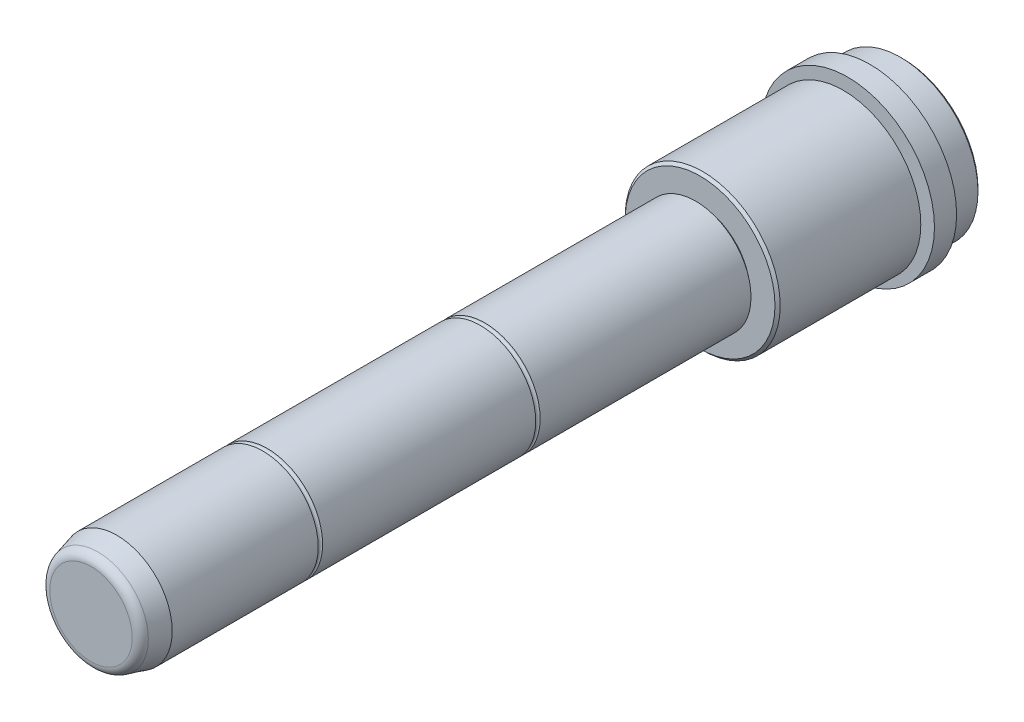
SolidWorks part; units mm, degrees
ref_plane "Płaszczyzna przednia" through (0, 0, 0) normal (0, 0, 1) x (1, 0, 0)
ref_plane "Płaszczyzna górna" through (0, 0, 0) normal (0, 1, 0) x (1, 0, 0)
ref_plane "Płaszczyzna prawa" through (0, 0, 0) normal (1, 0, 0) x (0, 0, -1)
sketch "Szkic1" plane through (0, 0, 0) normal (1, 0, 0) x (0, 0, -1)
  line L0 (-9, 0) -> (-9, 21)
  line L1 (-9, 21) -> (0, 21)
  line L2 (0, 21) -> (0, 0)
  line L3 (0, 0) -> (-9, 0)
  line L4 (0, 0) -> (-9, 0) construction
sketch "Szkic2" plane through (0, 0, 0) normal (1, 0, 0) x (0, 0, -1)
  line L0 (-0.7071, 21) -> (0, 20.2929)
  line L1 (0, 20.2929) -> (0, 21)
  line L2 (0, 21) -> (-0.7071, 21)
  line L3 (0, 0) -> (-9, 0) construction
sketch "Szkic3" plane through (0, 0, 0) normal (1, 0, 0) x (0, 0, -1)
  line L0 (-9, 18.9) -> (-7.8, 18.9)
  line L1 (-7.8, 18.9) -> (-7.8, 21)
  line L2 (-7.8, 21) -> (-9, 21)
  line L3 (-9, 21) -> (-9, 18.9)
  line L4 (0, 0) -> (-9, 0) construction
sketch "Szkic4" plane through (0, 0, 0) normal (1, 0, 0) x (0, 0, -1)
  line L0 (-15, 0) -> (-15, 23.5)
  line L1 (-15, 23.5) -> (-9, 23.5)
  line L2 (-9, 23.5) -> (-9, 0)
  line L3 (-9, 0) -> (-15, 0)
  line L4 (-9, 0) -> (-15, 0) construction
sketch "Szkic5" plane through (0, 0, 0) normal (1, 0, 0) x (0, 0, -1)
  line L0 (-55, 0) -> (-55, 21)
  line L1 (-55, 21) -> (-15, 21)
  line L2 (-15, 21) -> (-15, 0)
  line L3 (-15, 0) -> (-55, 0)
  line L4 (-15, 0) -> (-55, 0) construction
sketch "Szkic6" plane through (0, 0, 0) normal (1, 0, 0) x (0, 0, -1)
  line L0 (-16.2, 18.9) -> (-15, 18.9)
  line L1 (-15, 18.9) -> (-15, 21)
  line L2 (-15, 21) -> (-16.2, 21)
  line L3 (-16.2, 21) -> (-16.2, 18.9)
  line L4 (-15, 0) -> (-61, 0) construction
sketch "Szkic7" plane through (0, 0, 0) normal (1, 0, 0) x (0, 0, -1)
  line L0 (-55, 20.2929) -> (-54.2929, 21)
  line L1 (-54.2929, 21) -> (-55, 21)
  line L2 (-55, 21) -> (-55, 20.2929)
  line L3 (-9, 0) -> (-55, 0) construction
sketch "Szkic8" plane through (0, 0, 0) normal (1, 0, 0) x (0, 0, -1)
  line L0 (-220, 0) -> (-220, 15)
  line L1 (-220, 15) -> (-55, 15)
  line L2 (-55, 15) -> (-55, 0)
  line L3 (-55, 0) -> (-220, 0)
  line L4 (-55, 0) -> (-220, 0) construction
sketch "Szkic9" plane through (0, 0, 0) normal (1, 0, 0) x (0, 0, -1)
  line L0 (-56.2, 13.5) -> (-55, 13.5)
  line L1 (-55, 13.5) -> (-55, 15)
  line L2 (-55, 15) -> (-56.2, 15)
  line L3 (-56.2, 15) -> (-56.2, 13.5)
  line L4 (-55, 0) -> (-220, 0) construction
sketch "Szkic10" plane through (0, 0, 0) normal (1, 0, 0) x (0, 0, -1)
  line L0 (-220, 13.1244) -> (-213, 15)
  line L1 (-213, 15) -> (-220, 15)
  line L2 (-220, 15) -> (-220, 13.1244)
  line L3 (-55, 0) -> (-220, 0) construction
sketch "Szkic11" plane through (0, 0, 0) normal (1, 0, 0) x (0, 0, -1)
  line L0 (-218.11, 13.6308) -> (-220, 13.1244)
  line L1 (-220, 13.1244) -> (-220, 11.1677)
  line L2 (-55, 0) -> (-220, 0) construction
  arc A0 (-220, 11.1677) -> (-218.11, 13.6308) centre (-217.45, 11.1677) cw
sketch "Szkic12" plane through (0, 0, 0) normal (1, 0, 0) x (0, 0, -1)
  line L0 (-172.2571, 15) -> (-173.4571, 15)
  line L1 (-172.2571, 0) -> (-173.4571, 0) construction
  arc A0 (-173.4571, 15) -> (-172.2571, 15) centre (-172.8571, 15) ccw
sketch "Szkic13" plane through (0, 0, 0) normal (1, 0, 0) x (0, 0, -1)
  line L0 (-113.3286, 15) -> (-114.5286, 15)
  line L1 (-113.3286, 0) -> (-114.5286, 0) construction
  arc A0 (-114.5286, 15) -> (-113.3286, 15) centre (-113.9286, 15) ccw
ref_plane "Płaszczyzna1" through (0, 0, 9) normal (0, 0, 1) x (1, 0, 0)
revolve "Obrót1" add sketch "Szkic1" angle 360 about L4 reverse direction yes
revolve "Wycięcie-obrót1" cut sketch "Szkic2" angle 360 about L3 reverse direction yes
revolve "Wycięcie-obrót2" cut sketch "Szkic3" angle 360 about L4 reverse direction yes
revolve "Obrót2" add sketch "Szkic4" angle 360 about L4 reverse direction yes
revolve "Obrót3" add sketch "Szkic5" angle 360 about L4 reverse direction yes
revolve "Wycięcie-obrót3" cut sketch "Szkic6" angle 360 about L4 reverse direction yes
revolve "Wycięcie-obrót4" cut sketch "Szkic7" angle 360 about L3 reverse direction yes
revolve "Obrót4" add sketch "Szkic8" angle 360 about L4 reverse direction yes
revolve "Wycięcie-obrót5" cut sketch "Szkic9" angle 360 about L4 reverse direction yes
revolve "Wycięcie-obrót6" cut sketch "Szkic10" angle 360 about L3 reverse direction yes
revolve "Wycięcie-obrót7" cut sketch "Szkic11" angle 360 about L2 reverse direction yes
revolve "Wycięcie-obrót8" cut sketch "Szkic12" angle 360 about L1 reverse direction yes
revolve "Wycięcie-obrót9" cut sketch "Szkic13" angle 360 about L1 reverse direction yes
ref_plane "IP1 XY" through (0, 0, 9) normal (0, 0, 1) x (1, 0, 0)
ref_plane "IP1 XZ" through (0, 0, 0) normal (0, -1, 0) x (-1, 0, 0)
ref_plane "IP1 YZ" through (0, 0, 0) normal (1, 0, 0) x (0, 0, -1)
ref_axis "IP1 X" through (-80.9, 0, 9) along (1, 0, 0)
ref_axis "IP1 Y" through (0, -50, 9) along (0, 1, 0)
ref_axis "IP1 Z" through (0, 0, 80.9) along (0, 0, -1)
sketch3d "IP1"
  point P0 (0, 0, 9)
